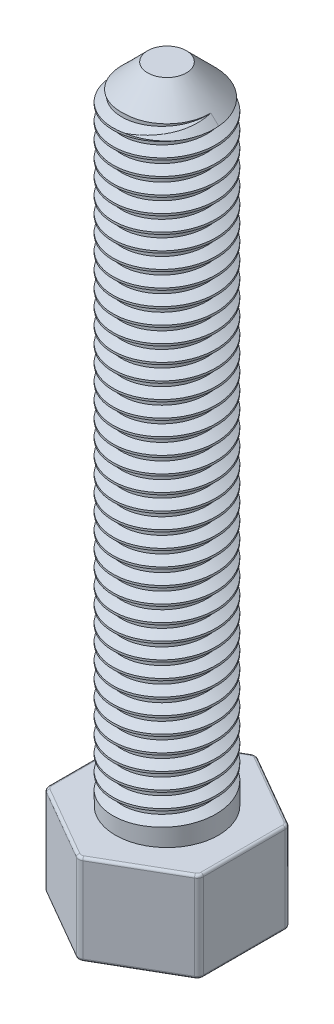
SolidWorks part; units mm, degrees
ref_plane "Спереди XY" through (0, 0, 0) normal (0, 0, 1) x (1, 0, 0)
ref_plane "Сверху XZ" through (0, 0, 0) normal (0, 1, 0) x (1, 0, 0)
ref_plane "Справа ZY" through (0, 0, 0) normal (1, 0, 0) x (0, 0, -1)
sketch "Эскиз1" plane through (0, 0, 0) normal (0, 1, 0) x (1, 0, 0)
  line L1 (0, 6.9282) -> (-6, 3.4641)
  line L2 (-6, 3.4641) -> (-6, -3.4641)
  line L3 (-6, -3.4641) -> (0, -6.9282)
  line L4 (0, -6.9282) -> (6, -3.4641)
  line L5 (6, -3.4641) -> (6, 3.4641)
  line L6 (6, 3.4641) -> (0, 6.9282)
  circle A0 centre (0, 0) radius 6 construction
  dimension "D1" = 12
extrude "Бобышка-Вытянуть1" add sketch "Эскиз1" along normal blind 7
sketch "Эскиз2" plane through (0, 7, 0) normal (0, 1, 0) x (1, 0, 0)
  circle A0 centre (0, 0) radius 4
  dimension "D1" = 8
extrude "Бобышка-Вытянуть2" add sketch "Эскиз2" along normal blind 50
chamfer "Фаска1" distance 2.5 angle 45 1 edges at (0, 57, 4)
thread "Резьба1" pitch 1.25 method cut profile "Профиль резьбы1" start angle 0, offset 2, length 47.5, pitch 1.25, diameter 8
ref_plane "Плоскость1" through (-4, 56.5, 0) normal (0, 0, 1) x (-1, 0, 0)
sketch "Профиль резьбы1" plane through (-4, 56.5, 0) normal (0, 0, 1) x (-1, 0, 0)
  line L0 (0, 0) -> (0, 1.25) construction
  line L11 (0, 0) -> (0, 1.0937)
  line L12 (0, 1.0937) -> (-0.6766, 0.7031)
  line L13 (-0.6766, 0.7031) -> (-0.6766, 0.3906)
  line L15 (-0.6766, 0.3906) -> (0, 0)
  line L17 (-0.6766, 0.5469) -> (0, 0.5469) construction
  point P2 (0, 0)
  dimension "Pitch" = 1.25
  dimension "Profile_Angle" = 60
  dimension "Profile_Land" = 0.3125
  dimension "Profile_Height" = 0.6766
fillet "Скругление1" radius 0.5 6 edges at (6, 3.5, 3.4641) (6, 3.5, -3.4641) (0, 3.5, -6.9282) (0, 3.5, 6.9282) (-6, 3.5, 3.4641) (-6, 3.5, -3.4641)
fillet "Скругление2" radius 0.2 12 edges at (5.933, 7, 3.4254) (3, 7, 5.1962) (0, 7, 6.8509) (-3, 7, 5.1962) (-5.933, 7, 3.4254) (-6, 7, 0) (-5.933, 7, -3.4254) (-3, 7, -5.1962) (0, 7, -6.8509) (3, 7, -5.1962) (5.933, 7, -3.4254) (6, 7, 0)
fillet "Скругление3" radius 0.2 12 edges at (5.933, 0, 3.4254) (3, 0, 5.1962) (0, 0, 6.8509) (-3, 0, 5.1962) (-5.933, 0, 3.4254) (-6, 0, 0) (-5.933, 0, -3.4254) (-3, 0, -5.1962) (0, 0, -6.8509) (3, 0, -5.1962) (5.933, 0, -3.4254) (6, 0, 0)
